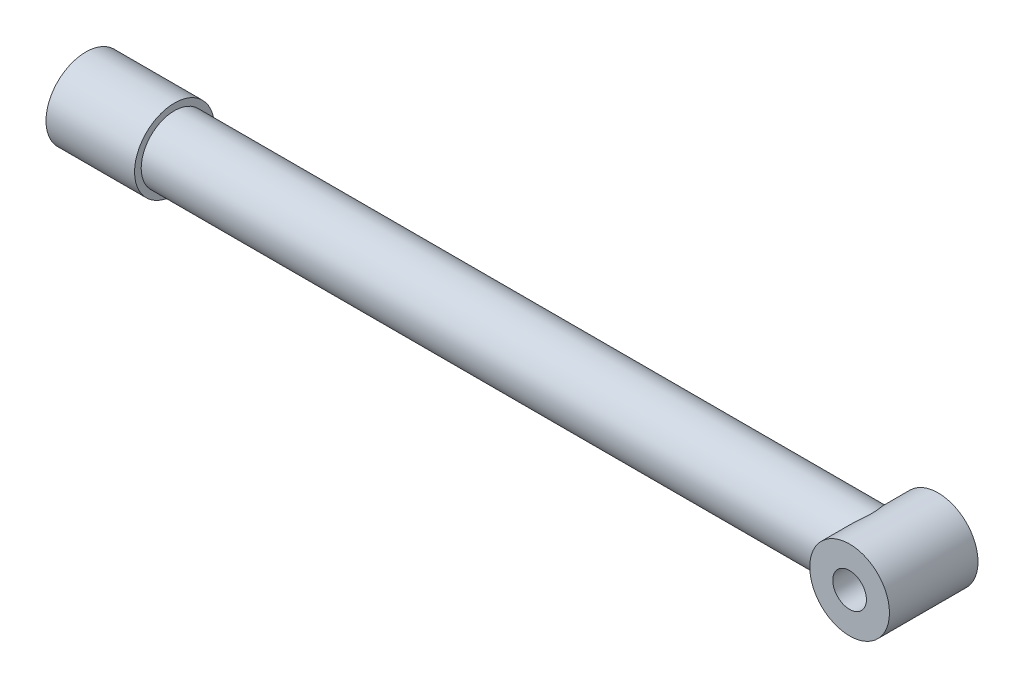
SolidWorks part; units mm, degrees
ref_plane "Front Plane" through (0, 0, 0) normal (0, 0, 1) x (1, 0, 0)
ref_plane "Top Plane" through (0, 0, 0) normal (0, 1, 0) x (1, 0, 0)
ref_plane "Right Plane" through (0, 0, 0) normal (1, 0, 0) x (0, 0, -1)
sketch "Sketch1" plane through (0, 0, 0) normal (0, 0, 1) x (1, 0, 0)
  line L0 (0, 0) -> (1825, 0) construction
  line L9 (1825, 0) -> (1825, 75)
  line L10 (1825, 75) -> (200, 75)
  line L11 (200, 75) -> (200, 90)
  line L12 (200, 90) -> (0, 90)
  line L13 (0, 90) -> (0, 51)
  line L14 (0, 51) -> (1750, 51)
  line L15 (1750, 51) -> (1750, 0)
  line L16 (1750, 0) -> (1825, 0)
  point P9 (1750, 25.5)
  dimension "D1" = 90
  dimension "D2" = 1825
  dimension "D3" = 200
  dimension "D4" = 1750
  dimension "D5" = 51
  dimension "D6" = 75
revolve "Revolve2" add sketch "Sketch1" angle 360 about L0
sketch "Sketch2" plane through (0, 0, 0) normal (0, 0, 1) x (1, 0, 0)
  line L0 (1825, -75) -> (1825, 75) construction
  circle A0 centre (1825, 0) radius 38
  circle A1 centre (1825, 0) radius 90
  dimension "D1" = 180
  dimension "D2" = 76
extrude "Boss-Extrude1" add sketch "Sketch2" along normal mid plane 200
extrude "Cut-Extrude1" cut sketch "Sketch2<2>" against normal through all both and the other way through all contours A0
sketch "Sketch2<2>" plane through (0, 0, 0) normal (0, 0, 1) x (1, 0, 0) same geometry as "Sketch2"
